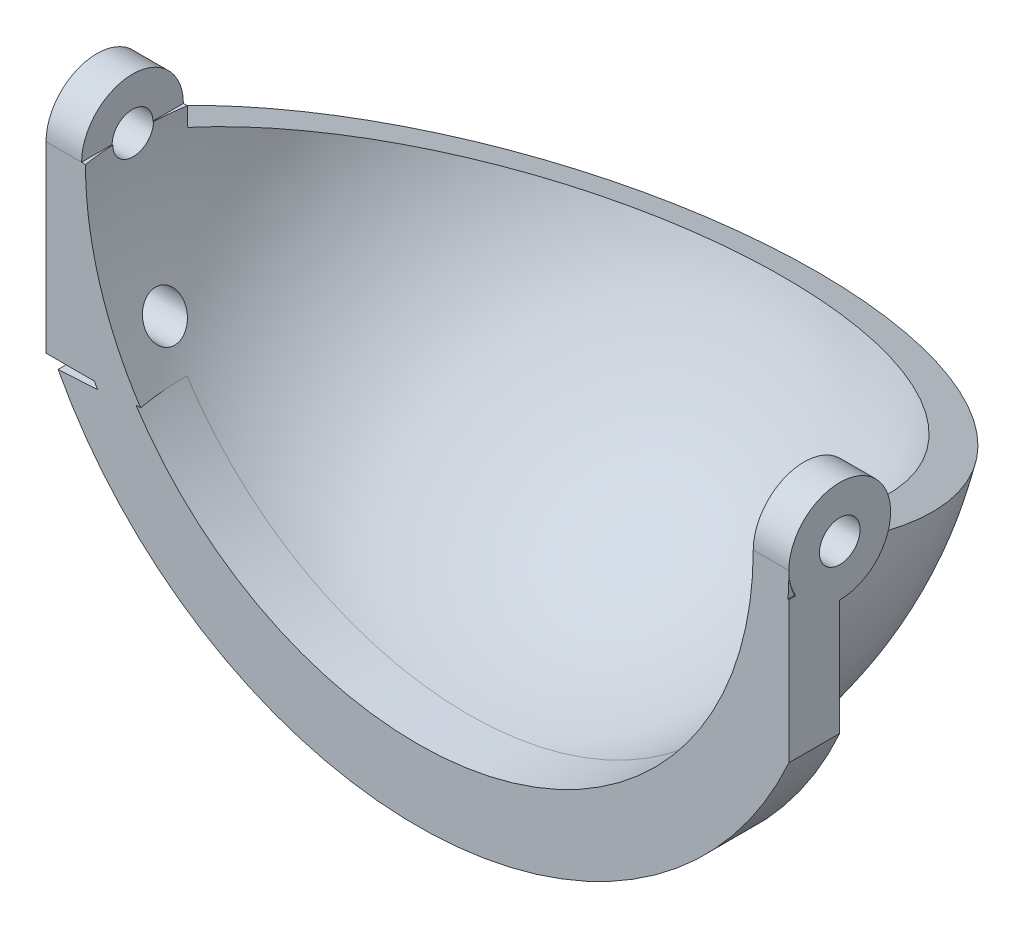
SolidWorks part; units mm, degrees
ref_plane "前视基准面" through (0, 0, 0) normal (0, 0, 1) x (1, 0, 0)
ref_plane "上视基准面" through (0, 0, 0) normal (0, 1, 0) x (1, 0, 0)
ref_plane "右视基准面" through (0, 0, 0) normal (1, 0, 0) x (0, 0, -1)
sketch "草图1" plane through (0, 0, 0) normal (0, 0, 1) x (1, 0, 0)
  line L0 (18.25, 0) -> (-18.25, 0) construction
  line L1 (-18.25, 0) -> (-16.5, 0)
  line L2 (16.5, 0) -> (18.25, 0)
  circle A0 centre (0, 0) radius 18.25 construction
  circle A1 centre (0, 0) radius 16.5 construction
  arc A2 (-18.25, 0) -> (18.25, 0) centre (0, 0) ccw
  arc A3 (-16.5, 0) -> (16.5, 0) centre (0, 0) ccw
  dimension "D1" = 33
  dimension "D2" = 36.5
extrude "凸台-拉伸1" add sketch "草图1" along normal blind 2.5
sketch "草图2" plane through (0, 0, 0) normal (0, 0, -1) x (-1, 0, 0)
  line L0 (-16.5, 0) -> (16.5, 0) construction
  line L1 (16.5, 0) -> (18.25, 0) construction
  line L2 (-18.25, 0) -> (-16.5, 0) construction
  line L3 (-17.375, 0) -> (-16.5, 0)
  line L4 (17.375, 0) -> (16.5, 0)
  line L5 (17.375, 0) -> (18.25, 0)
  line L6 (-17.375, 0) -> (-18.25, 0)
  arc A0 (-16.5, 0) -> (16.5, 0) centre (0, 0) ccw
  arc A3 (-18.25, 0) -> (18.25, 0) centre (0, 0) ccw construction
  arc A4 (18.25, 0) -> (-18.25, 0) centre (0, 0) cw
revolve "旋转1" add sketch "草图2" angle 70 about L0 reverse direction yes
sketch "草图4" plane through (0, 0, 0) normal (1, 0, 0) x (0, 0, -1)
  circle A0 centre (0, 0) radius 1
  circle A1 centre (0, 0) radius 2.5
extrude "凸台-拉伸2" add sketch "草图4" along normal blind 18.25 and the other way blind 18.25
sketch "草图7" plane through (0, 0, 0) normal (1, 0, 0) x (0, 0, -1)
  circle A0 centre (0, 0) radius 1
  circle A1 centre (0, 0) radius 2.5
extrude "切除-拉伸1" cut sketch "草图7" against normal blind 16.5 and the other way blind 16.5
sketch "草图8" plane through (0, 0, 0) normal (1, 0, 0) x (0, 0, -1)
  circle A0 centre (0, 0) radius 1
extrude "切除-拉伸2" cut sketch "草图8" against normal blind 100 and the other way blind 100
sketch "草图9" plane through (-18.25, 0, 0) normal (-1, 0, 0) x (0, 0, 1)
  line L0 (1, 0) -> (2.5, 0)
  line L1 (-1, 0) -> (-2.5, 0)
  line L2 (0, 0) -> (0, -7) construction
  line L3 (2.5, 0) -> (2.5, -9)
  line L4 (2.5, -9) -> (-2.5, -9)
  line L5 (-2.5, -9) -> (-2.5, 0)
  circle A0 centre (0, 0) radius 1 construction
  circle A1 centre (0, 0) radius 2.5 construction
  circle A2 centre (0, -7) radius 1
  arc A3 (1, 0) -> (-1, 0) centre (0, 0) cw
extrude "凸台-拉伸3" add sketch "草图9" against normal blind 5
sketch "草图12" plane through (-18.25, 0, 0) normal (-1, 0, 0) x (0, 0, 1)
  circle A0 centre (0, -7) radius 1
extrude "切除-拉伸3" cut sketch "草图12" against normal blind 5
sketch "草图13" plane through (0, 0, 0) normal (0, 0, 1) x (1, 0, 0)
  line L0 (16.5, 0) -> (-16.5, 0)
  circle A0 centre (0, 0) radius 16.5 construction
  arc A1 (-16.5, 0) -> (16.5, 0) centre (0, 0) ccw
revolve "切除-旋转1" cut sketch "草图13" angle 360 about L0
sketch "草图14" plane through (0, 0, 0) normal (0, 0, 1) x (1, 0, 0)
  line L0 (16.5, -1) -> (19.9457, -1.4733)
  line L1 (-13.7501, -9.1752) -> (-17.6571, -9.3929)
  arc A0 (16.5, -1) -> (-13.7501, -9.1752) centre (0, 0) cw
  arc A1 (19.9457, -1.4733) -> (-17.6571, -9.3929) centre (0, 0) cw
  point P7 (-17.2479, -9.1752)
extrude "凸台-拉伸4" add sketch "草图14" along normal blind 2.5
sketch "草图15" plane through (0, 0, 0) normal (0, 0, -1) x (-1, 0, 0)
  line L0 (-19.9457, -1.4733) -> (-18.25, -1.2404)
  line L1 (-18.25, -1.2404) -> (-18.25, -11.0431)
  line L2 (-18.25, -11.0431) -> (-22.7874, -5.6395)
  line L3 (-22.7874, -5.6395) -> (-19.9457, -1.4733)
extrude "切除-拉伸4" cut sketch "草图15" against normal blind 2.5
